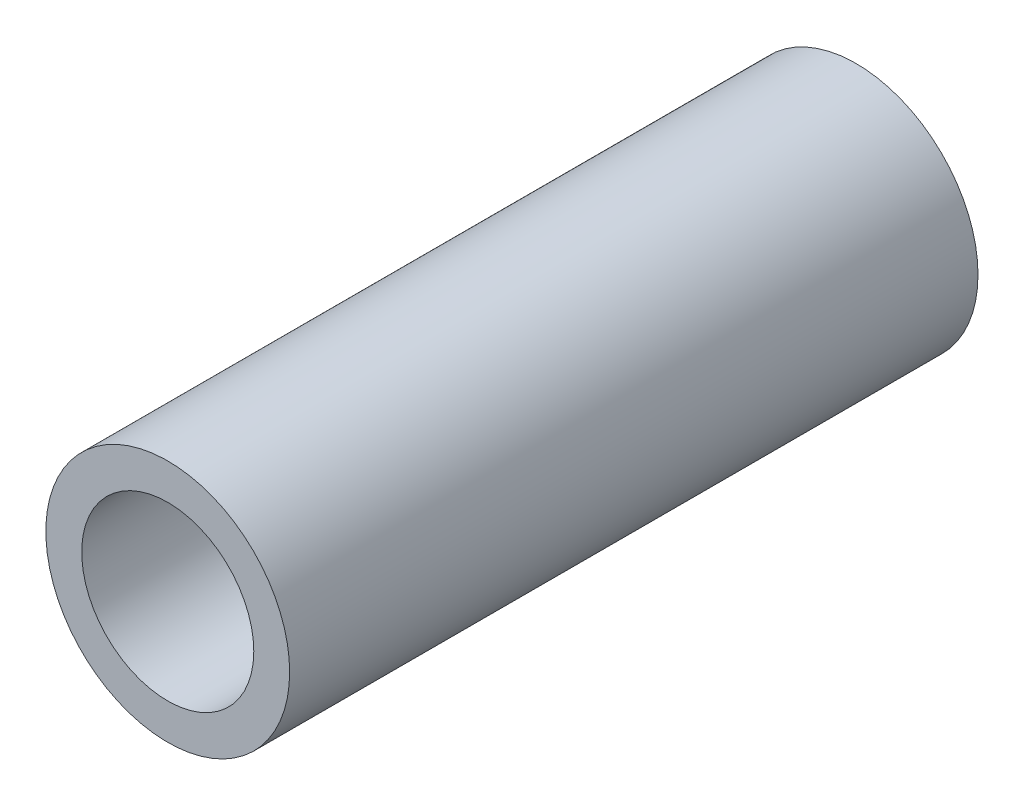
SolidWorks part; units mm, degrees
material "Silicon Rubber"
ref_plane "X-Y Datum" through (0, 0, 0) normal (0, 0, 1) x (1, 0, 0)
ref_plane "X-Z Datum" through (0, 0, 0) normal (0, 1, 0) x (1, 0, 0)
ref_plane "Y-Z Datum" through (0, 0, 0) normal (1, 0, 0) x (0, 0, -1)
sketch3d "3DSketch1"
  line L0 (0, 0, 0) -> (0, 0, 76.2)
  dimension "D1" = 76.2
sweep "Sweep1" add path "3DSketch1" circular profile diameter 26.9875 parameters "D3"=26.9875
sweep "Cut-Sweep1" cut path "3DSketch1<2>" circular profile diameter 19.05 parameters "D3"=19.05
sketch3d "3DSketch1<2>" same geometry as "3DSketch1"
sketch3d "3DSketch2"
  circle A0 centre (0, 0, 50.8) radius 9.525 construction
  circle A1 centre (0, 0, 25.4) radius 9.525 construction
  circle A2 centre (0, 0, 76.2) radius 13.4937 construction
  circle A5 centre (0, 0, 0) radius 9.525 construction
  point P4 (0, 0, 15.875)
  point P5 (0, 0, -9.525)
  point P8 (0, 0, 41.275)
  point P12 (0, 0, 89.6937)
  dimension "D1" = 25.4
  dimension "D2" = 25.4
